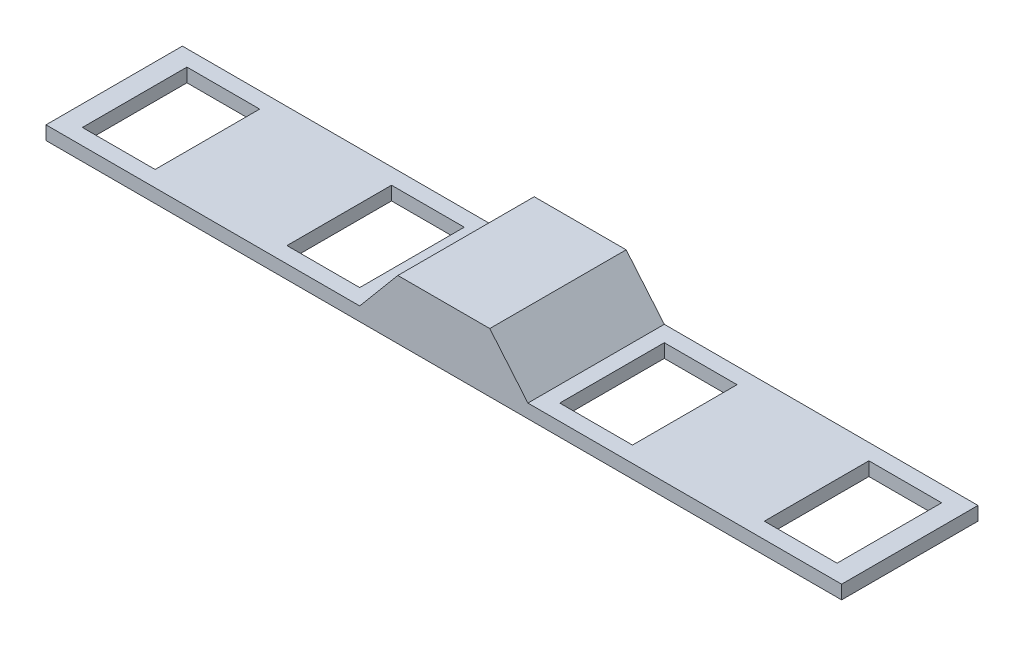
SolidWorks part; units mm, degrees
ref_plane "Front Plane" through (0, 0, 0) normal (0, 0, 1) x (1, 0, 0)
ref_plane "Top Plane" through (0, 0, 0) normal (0, 1, 0) x (1, 0, 0)
ref_plane "Right Plane" through (0, 0, 0) normal (1, 0, 0) x (0, 0, -1)
sketch "Croquis1" plane through (0, 0, 0) normal (0, 1, 0) x (1, 0, 0)
  line L0 (-83, -11.5) -> (-83, 11.5)
  line L1 (-87.5, -15) -> (87.5, -15)
  line L2 (-87.5, -15) -> (-87.5, 15)
  line L3 (-87.5, 15) -> (87.5, 15)
  line L4 (87.5, -15) -> (87.5, 15)
  line L5 (-87.5, -15) -> (87.5, 15) construction
  line L6 (-87.5, 15) -> (87.5, -15) construction
  line L11 (22, -11.5) -> (22, 11.5)
  line L12 (-38, -11.5) -> (-22, -11.5)
  line L13 (0, 0) -> (0, 50000) construction
  line L18 (-38, -11.5) -> (-38, 11.5)
  line L19 (-38, 11.5) -> (-22, 11.5)
  line L20 (-22, -11.5) -> (-22, 11.5)
  line L21 (-38, -11.5) -> (-22, 11.5) construction
  line L22 (-38, 11.5) -> (-22, -11.5) construction
  line L23 (38, -11.5) -> (22, -11.5)
  line L24 (38, -11.5) -> (38, 11.5)
  line L25 (38, 11.5) -> (22, 11.5)
  line L26 (-83, 11.5) -> (-67, 11.5)
  line L27 (-67, -11.5) -> (-67, 11.5)
  line L28 (-83, -11.5) -> (-67, -11.5)
  line L29 (83, 11.5) -> (67, 11.5)
  line L30 (67, -11.5) -> (67, 11.5)
  line L31 (83, -11.5) -> (67, -11.5)
  line L32 (83, -11.5) -> (83, 11.5)
  point P0 (0, 0)
  point P5 (-30, 0)
  dimension "D1" = 175
  dimension "D2" = 16
  dimension "D3" = 23
  dimension "D4" = 30
  dimension "D5" = 2
  dimension "D6" = 2
extrude "Saliente-Extruir1" add sketch "Croquis1" along normal blind 3
sketch "Croquis2" plane through (0, 3, 0) normal (0, 1, 0) x (1, 0, 0)
  line L0 (87.5, 15) -> (-87.5, 15) construction
  line L1 (-18.5, -15) -> (18.5, -15)
  line L2 (-18.5, -15) -> (-18.5, 15)
  line L3 (-18.5, 15) -> (18.5, 15)
  line L4 (18.5, -15) -> (18.5, 15)
  line L5 (-18.5, -15) -> (18.5, 15) construction
  line L6 (-18.5, 15) -> (18.5, -15) construction
  point P0 (0, 0)
  dimension "D1" = 37
extrude "Saliente-Extruir2" add sketch "Croquis2" along normal blind 10
chamfer "Chaflán1" distance 10 angle 40 2 edges at (18.5, 13, 0) (-18.5, 13, 0) first distance on face at (18.5, 8, 0) first distance on face at (-18.5, 8, 0)
